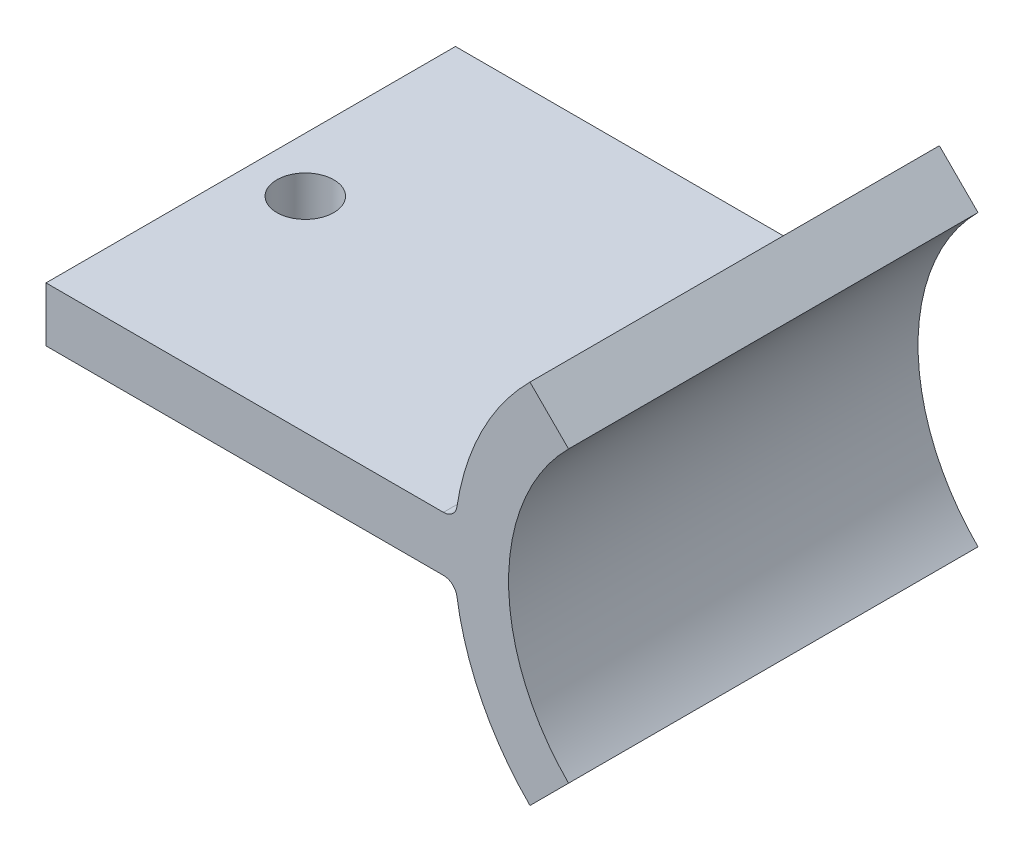
SolidWorks part; units mm, degrees
ref_plane "Top Plane" through (0, 0, 0) normal (0, 0, 1) x (1, 0, 0)
ref_plane "Right Plane" through (0, 0, 0) normal (0, 1, 0) x (1, 0, 0)
ref_plane "Front Plane" through (0, 0, 0) normal (1, 0, 0) x (0, 0, -1)
ref_axis "x-axis" through (-88.99, 0, 0) along (1, 0, 0)
ref_axis "y-axis" through (0, -55, 0) along (0, 1, 0)
ref_axis "z-axis" through (0, 0, 55) along (0, 0, -1)
sketch "Sketch1" plane through (0, 0, 0) normal (0, 0, 1) x (1, 0, 0)
  line L0 (5.5796, -13.4704) -> (1.9875, -17.0625)
  line L2 (5.5796, -13.4704) -> (19.05, 0) construction
  line L4 (19.05, 0) -> (5.5796, 13.4704) construction
  line L5 (5.5796, 13.4704) -> (1.9875, 17.0625)
  line L6 (55, 0) -> (-55, 0) construction
  line L7 (5.5796, -13.4704) -> (5.5796, 13.4704) construction
  line L8 (0, 0) -> (-43.0459, 0) construction
  line L9 (-4.9459, -2.54) -> (-43.0459, -2.54)
  line L11 (-4.9459, 2.54) -> (-43.0459, 2.54)
  line L12 (-43.0459, -2.54) -> (-43.0459, 2.54)
  arc A0 (5.5796, -13.4704) -> (5.5796, 13.4704) centre (19.05, 0) cw
  arc A1 (1.9875, -17.0625) -> (-4.9459, -2.54) centre (19.05, 0) cw
  arc A2 (-4.9459, 2.54) -> (1.9875, 17.0625) centre (19.05, 0) cw
  dimension "D1" = 90
  dimension "D2" = 5.08
  dimension "D3" = 19.05
  dimension "D4" = 38.1
  dimension "D5" = 5.08
extrude "Boss-Extrude1" add sketch "Sketch1" along normal mid plane 38.1
ref_axis "Axis2" through (19.05, 0, 19.05) along (0, 0, -1)
sketch "Sketch3" plane through (0, 0, 0) normal (0, 1, 0) x (1, 0, 0)
  line L0 (0, -12.7) -> (0, 12.7) construction
  line L1 (-5.08, 12.7) -> (0, 12.7) construction
  line L2 (-7.62, 15.24) -> (-5.08, 15.24)
  line L3 (-7.62, 15.24) -> (-7.62, 10.16)
  line L4 (-7.62, 10.16) -> (-5.08, 10.16)
  line L5 (-5.08, 15.24) -> (-5.08, 10.16)
  line L6 (-7.62, 15.24) -> (-5.08, 15.24)
  line L7 (-7.62, 10.16) -> (-5.08, 10.16)
  line L8 (-12.5504, 0) -> (12.5504, 0) construction
  line L9 (-5.08, -12.7) -> (0, -12.7) construction
  line L10 (-5.08, -15.24) -> (-5.08, -10.16)
  line L11 (-7.62, -10.16) -> (-5.08, -10.16)
  line L12 (-7.62, -15.24) -> (-7.62, -10.16)
  line L13 (-7.62, -15.24) -> (-5.08, -15.24)
  point P4 (0, 0)
  dimension "D1" = 5.08
  dimension "D2" = 2.54
  dimension "D3" = 5.08
  dimension "D4" = 25.4
revolve "Cut-Revolve1" cut sketch "Sketch3" angle 360 about axis through (19.05, 0, 19.05) along (0, 0, -1) region at (-6.35, 0, -12.7) region at (-6.35, 0, 12.7)
hole_wizard "M5 Clearance Hole1" positions "Sketch6" profile "Sketch7" hole size "M5" standard "ANSI Metric" end condition through all
sketch "Sketch6" plane through (0, 2.54, 0) normal (0, 1, 0) x (1, 0, 0)
  line L4 (-43.0459, -19.05) -> (-43.0459, 19.05) construction
  point P0 (-37.9659, 0)
  point P15 (0, 0)
  point P16 (-12.0464, 12.7908)
  point P17 (-11.9392, 12.7)
  point P18 (0, 0)
  point P19 (0, 0)
  point P23 (-7.1317, 12.7)
  point P26 (0, 0)
  point P27 (-50.6659, 12.7)
  point P28 (0, 0)
  point P29 (0, 0)
  point P30 (-50.6659, 0)
  dimension "D1" = 5.08
sketch "Sketch7" plane through (-37.9659, 2.54, 0) normal (1, 0, 0) x (0, 0, 1)
  line L0 (0, 0) -> (0, 19.6025)
  line L1 (0, 19.6025) -> (2.65, 19.6025)
  line L2 (2.65, 19.6025) -> (2.65, 0)
  line L5 (2.65, 0) -> (0, 0)
  line L11 (0, -6.35) -> (0, 107.95) construction
  dimension "Thru Hole Dia." = 5.3
  dimension "Thru Hole Depth" = 19.6025
fillet "Fillet1" radius 1.27 14 edges at (-7.62, 0, 10.16) (-5.08, 0, 10.16) (-5.08, 0, 15.24) (-7.62, 0, 15.24) (-5.08, 0, -10.16) (-7.62, 0, -10.16) (-7.62, 0, -15.24) (-5.08, 0, -15.24) (-4.9459, -2.54, 0) (-4.9459, -2.54, 17.145) (-4.9459, 2.54, -17.145) (-4.9459, 2.54, 0) (-4.9459, 2.54, 17.145) (-4.9459, -2.54, -17.145)
